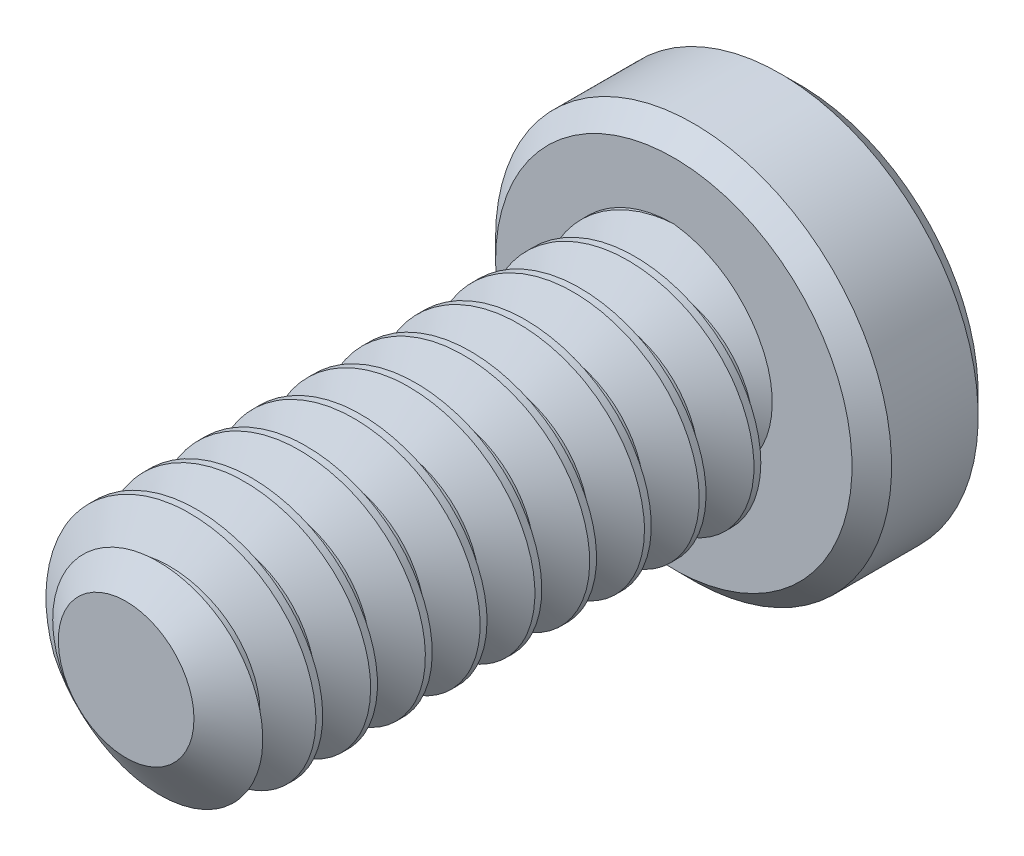
SolidWorks part; units mm, degrees
note: '?' marks a value the reader was unsure of.
other "DetailItem1"
ref_plane "Front Plane" through (0, 0, 0) normal (0, 0, 1) x (1, 0, 0)
ref_plane "Top Plane" through (0, 0, 0) normal (0, 1, 0) x (1, 0, 0)
ref_plane "Right Plane" through (0, 0, 0) normal (1, 0, 0) x (0, 0, -1)
sketch "Sketch1" plane through (0, 0, 0) normal (0, 0, 1) x (1, 0, 0)
  circle A0 centre (0, 0) radius 1.7526
  dimension "OD" = 3.5052
extrude "Extrude1" add sketch "Sketch1" against normal blind 7.9375
sketch "Sketch2" plane through (0, 0, 0) normal (0, 0, 1) x (1, 0, 0)
  circle A0 centre (0, 0) radius 1.7526 construction
  circle A1 centre (0, 0) radius 1.7526
curve "Helix/Spiral1" pitch 0.7937 height 8.7312 turns 11 parameters "pitch"=0.7937
sketch "Sketch3" plane through (0, 0, 0) normal (1, 0, 0) x (0, 0, -1)
  line L0 (-0.6945, 1.7526) -> (-0.3969, 1.237)
  line L1 (-0.3969, 1.237) -> (-0.2977, 1.237)
  line L2 (-0.2977, 1.237) -> (0, 1.7526)
  line L3 (-0.6945, 1.7526) -> (0, 1.7526)
  line L4 (-0.3473, 1.7526) -> (-0.3473, 1.237) construction
  line L5 (-0.5457, 1.4948) -> (-0.1488, 1.4948) construction
  line L6 (0, 1.7526) -> (0, -1.7526) construction
  dimension "D1" = 0.0992
  dimension "D2" = 0.3969
  dimension "D3" = 60
sweep "Cut-Sweep1" cut profiles "Sketch3" path "Helix/Spiral1"
sketch "Sketch4" plane through (0, 0, 0) normal (1, 0, 0) x (0, 0, -1)
  line L0 (0.5388, 1.7526) -> (0, 0.983)
  line L1 (0, 0.983) -> (0, 1.7526)
  line L2 (0.5388, 1.7526) -> (0, 1.7526)
  line L3 (-0.6945, 1.7526) -> (0, 1.7526) construction
  line L4 (0, 0) -> (7.0209, 0) construction
  dimension "D1" = 55
  dimension "D2" = 0.254
revolve "Cut-Revolve1" cut sketch "Sketch4" angle 360 about L4
sketch "Sketch6" plane through (0, 0, -7.9375) normal (0, 0, -1) x (-1, 0, 0)
  circle A0 centre (0, 0) radius 2.8702
  dimension "head dia" = 5.7404
extrude "Extrude2" add sketch "Sketch6" along normal blind 1.8288
sketch "Sketch7" plane through (0, 0, -9.7663) normal (0, 0, -1) x (-1, 0, 0)
  line L1 (0, 0.9165) -> (-0.7937, 0.4583)
  line L2 (-0.7937, 0.4583) -> (-0.7937, -0.4583)
  line L3 (-0.7937, -0.4583) -> (0, -0.9165)
  line L4 (0, -0.9165) -> (0.7937, -0.4583)
  line L5 (0.7937, -0.4583) -> (0.7937, 0.4583)
  line L6 (0.7937, 0.4583) -> (0, 0.9165)
  circle A0 centre (0, 0) radius 0.7937 construction
  dimension "hex dia" = 1.5875
extrude "Cut-Extrude1" cut sketch "Sketch7" against normal blind 1.1906
sketch "Sketch8" plane through (0, 0, -9.7663) normal (0, 0, -1) x (-1, 0, 0)
  circle A0 centre (0, 0) radius 0.9165
extrude "Cut-Extrude2" cut sketch "Sketch8" against normal through all draft 45
chamfer "Chamfer1" distance 0.287 angle 45 2 edges at (-2.8702, 0, -9.7663) (-2.8702, 0, -7.9375)
sketch "Sketch10" plane through (0, 0, -7.9375) normal (0, 0, 1) x (1, 0, 0)
  circle A1 centre (0, 0) radius 1.7526
  circle A2 centre (0, 0) radius 1.7526
  dimension "D1" = 0
ref_plane "Plane1" through (0, 0, 0) normal (0, 0, 1) x (1, 0, 0)
extrude "partial thread" [suppressed] add sketch "Sketch10" along normal up to surface (12.7 mm away) separate body
chamfer "Chamfer2" [suppressed] distance 0.0701 angle 45
combine bodies "Combine1" [suppressed] operation type? add bodies to combine 107 108
sketch "Sketch9" plane through (0, 0, 0) normal (1, 0, 0) x (0, 0, -1)
  line L0 (0, 1.7526) -> (0, -1.7526) construction
  line L1 (1.9844, 1.7526) -> (1.9844, -1.7526) construction
  dimension "D1" = 1.9844
sketch "Sketch11" plane through (0, 0, -7.9375) normal (0, 0, 1) x (1, 0, 0)
  circle A0 centre (0, 0) radius 3.175
  dimension "Shoulder Diameter" = 6.35
equation "\"D3@Helix/Spiral1\" = \"screw length@Extrude1\"+\"pitch@Helix/Spiral1\""
equation "\"D1@Sketch3\" = \"pitch@Helix/Spiral1\"*.125"
equation "\"D2@Sketch3\" = \"pitch@Helix/Spiral1\"*.5"
equation "\"D1@Cut-Extrude1\" = \"hex dia@Sketch7\"*.75"
equation "\"D1@Chamfer1\" = \"head dia@Sketch6\"*.05"
equation "\"D1@Sketch9\" = \"pitch@Helix/Spiral1\"*2.5"
equation "\"D1@Chamfer2\"=\"OD@Sketch1\"*.02"
